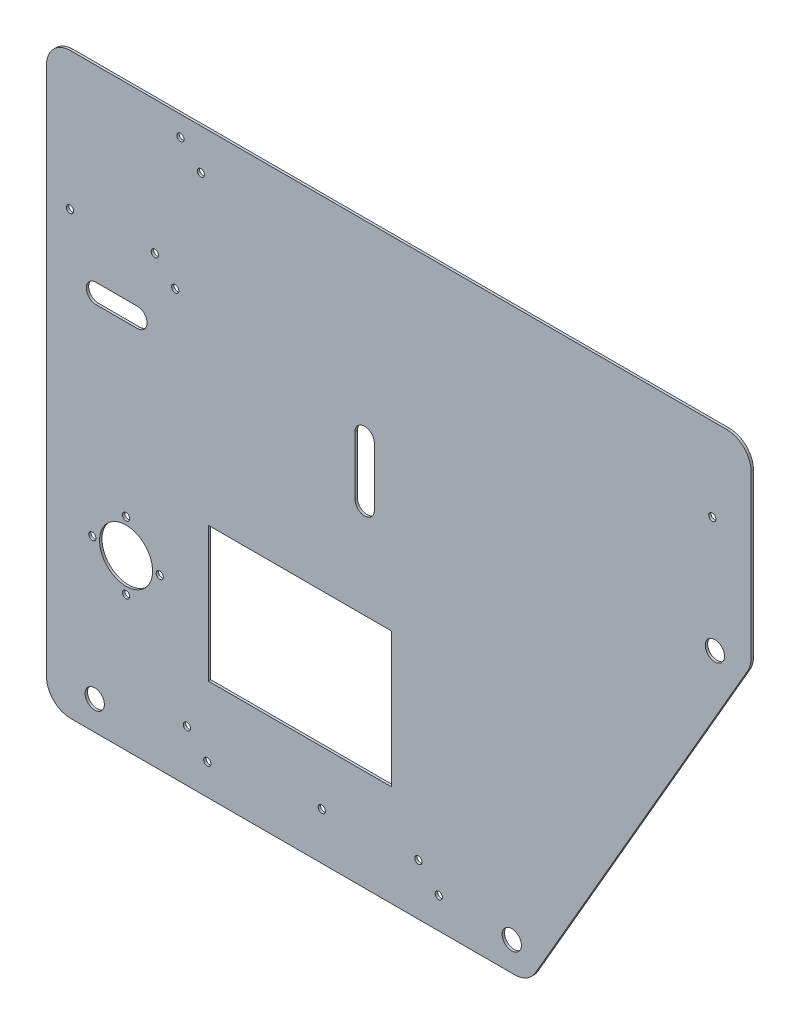
SolidWorks part; units mm, degrees
ref_plane "Front Plane" through (0, 0, 0) normal (0, 0, 1) x (1, 0, 0)
ref_plane "Top Plane" through (0, 0, 0) normal (0, 1, 0) x (1, 0, 0)
ref_plane "Right Plane" through (0, 0, 0) normal (1, 0, 0) x (0, 0, -1)
sketch "Sketch1" plane through (0, 0, 0) normal (0, 0, 1) x (1, 0, 0)
  line L0 (100, 80) -> (192.376, 80)
  line L1 (-100, -80) -> (100, -80)
  line L2 (-100, -80) -> (-100, 80)
  line L3 (-100, 80) -> (100, 80)
  line L4 (100, -80) -> (100, 80)
  line L5 (-100, -80) -> (100, 80) construction
  line L6 (-100, 80) -> (100, -80) construction
  line L7 (192.376, 80) -> (100, -80)
  line L8 (100, 80) -> (100, -80)
  line L10 (-100, 80) -> (192.376, 80)
  line L11 (-100, 80) -> (-100, 110)
  line L12 (-100, 110) -> (192.376, 110)
  line L13 (192.376, 80) -> (192.376, 110)
  point P0 (0, 0)
  dimension "D1" = 160
  dimension "D2" = 200
  dimension "D3" = 30
  dimension "D4" = 30
extrude "Boss-Extrude1" add sketch "Sketch1" along normal blind 1 contours L1 L4 L3 L2 | L7 L0 L4 | L11 L10 L13 L12 region at (0, 0, 0) region at (130.792, 26.6667, 0)
sketch "Sketch2" plane through (0, 0, 1) normal (0, 0, 1) x (1, 0, 0)
  line L0 (-100, -80) -> (100, -80) construction
  line L1 (192.376, 80) -> (100, -80) construction
  line L2 (-100, -80) -> (-100, 110) construction
  line L3 (-100, 110) -> (192.376, 110) construction
  line L4 (-79.5166, 78) -> (-62.3003, 78) construction
  line L7 (-100, -80) -> (-100, 110) construction
  line L8 (-29.8584, 15) -> (-29.8584, -35) construction
  line L9 (-79.5166, 82) -> (-62.3003, 82)
  line L10 (-79.5166, 74) -> (-62.3003, 74)
  line L11 (-32.8584, 18) -> (43.1416, 18)
  line L12 (-32.8584, 18) -> (-32.8584, -38)
  line L13 (-32.8584, -38) -> (43.1416, -38)
  line L14 (43.1416, 18) -> (43.1416, -38)
  line L15 (20.1416, 15) -> (-29.8584, 15) construction
  line L17 (40.1416, -35) -> (40.1416, 15) construction
  line L18 (32.0262, 82) -> (32.0262, 57.7776) construction
  line L19 (36.0262, 82) -> (36.0262, 57.7776)
  line L20 (28.0262, 82) -> (28.0262, 57.7776)
  circle A0 centre (93.0718, -68) radius 4
  circle A1 centre (177.3649, 78) radius 4
  circle A2 centre (-67, -10) radius 11
  circle A3 centre (-80, -68) radius 4
  circle A4 centre (-53, -10) radius 1.5
  circle A5 centre (-67, 4) radius 1.5
  circle A6 centre (-81, -10) radius 1.5
  circle A7 centre (-67, -24) radius 1.5
  circle A10 centre (32.0262, 70) radius 4 construction
  arc A11 (-79.5166, 82) -> (-79.5166, 74) centre (-79.5166, 78) ccw
  arc A12 (-62.3003, 74) -> (-62.3003, 82) centre (-62.3003, 78) ccw
  circle A32 centre (62.7961, -67.2426) radius 1.5
  circle A33 centre (54.3108, -58.7574) radius 1.5
  circle A34 centre (-33.2742, -67.2426) radius 1.5
  circle A35 centre (-41.7595, -58.7574) radius 1.5
  circle A36 centre (14.2259, -60.5) radius 1.5
  circle A37 centre (-46.589, 96.1388) radius 1.5
  circle A38 centre (-55.0743, 104.6241) radius 1.5
  circle A39 centre (-90.2956, 102.8814) radius 1.5
  circle A40 centre (176.3056, 125.4889) radius 1.5
  arc A41 (36.0262, 82) -> (28.0262, 82) centre (32.0262, 82) ccw
  arc A42 (28.0262, 57.7776) -> (36.0262, 57.7776) centre (32.0262, 57.7776) ccw
  point P12 (-70.9085, 78)
  point P65 (32.0262, 69.8888)
  dimension "D3" = 8
  dimension "D4" = 8
  dimension "D9" = 22
  dimension "D10" = 8
  dimension "D12" = 3
  dimension "D13" = 3
  dimension "D14" = 3
  dimension "D15" = 3
  dimension "D16" = 14
  dimension "D20" = 4
  dimension "D22" = 8
  dimension "D23" = 3
  dimension "D24" = 20
  dimension "D25" = 3
  dimension "D1" = 12
  dimension "D2" = 12
  dimension "D5" = 32
  dimension "D6" = 12
  dimension "D7" = 33
  dimension "D8" = 70
  dimension "D11" = 12
  dimension "D17" = 14
  dimension "D18" = 14
  dimension "D19" = 14
  dimension "D21" = 40
  dimension "D26" = 3
  dimension "D27" = 3
  dimension "D28" = 8
  dimension "D29" = 3
extrude "Cut-Extrude1" cut sketch "Sketch2" against normal blind 3
sketch "Sketch3" plane through (0, 0, 1) normal (0, 0, 1) x (1, 0, 0)
  line L0 (192.376, 80) -> (192.376, 110) construction
  line L1 (-100, 110) -> (192.376, 110)
  line L2 (-100, 110) -> (-100, 160)
  line L3 (-100, 160) -> (192.376, 160)
  line L4 (192.376, 110) -> (192.376, 160)
  dimension "D1" = 50
extrude "Boss-Extrude2" add sketch "Sketch3" against normal blind 1
fillet "Fillet1" radius 10 5 edges at (100, -80, 0.5) (-100, -80, 0.5) (-100, 160, 0.5) (192.376, 160, 0.5) (192.376, 80, 0.5)
sketch "Sketch4" plane through (0, 0, 1) normal (0, 0, 1) x (1, 0, 0)
  circle A2 centre (-44.4423, 151.6241) radius 1.5
  circle A3 centre (-35.957, 143.1388) radius 1.5
  circle A4 centre (176.3056, 125.4889) radius 1.5
  dimension "D1" = 3
extrude "Cut-Extrude2" cut sketch "Sketch4" against normal blind 11
